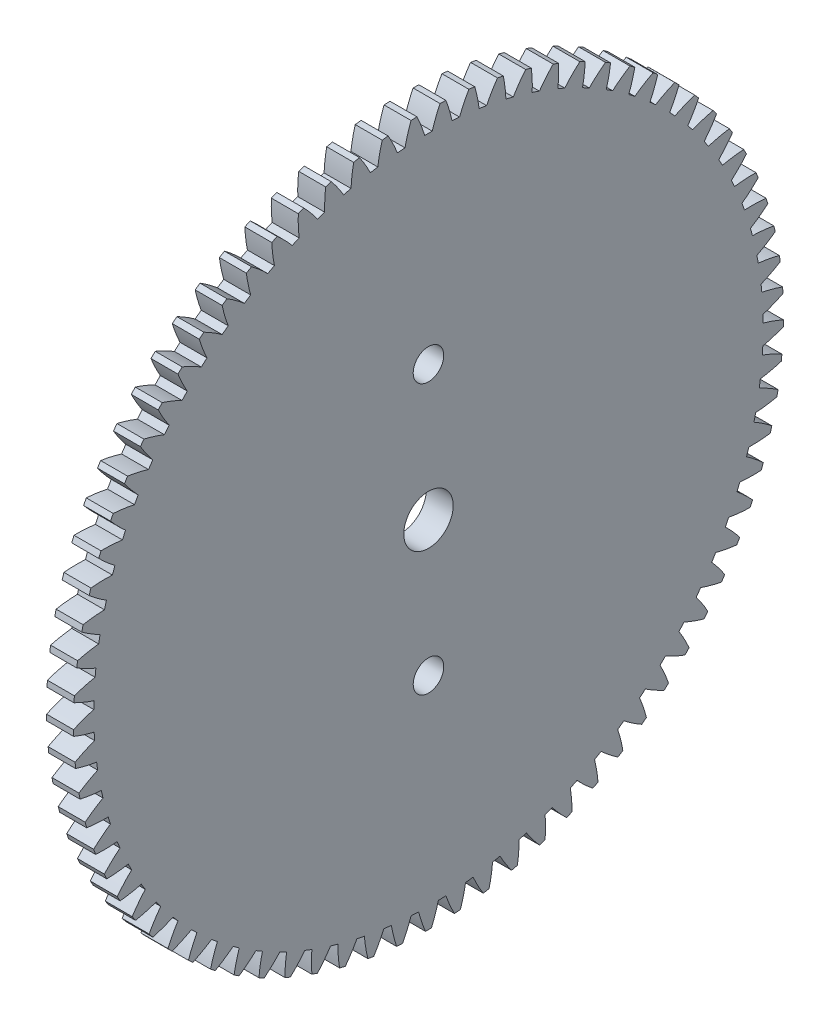
SolidWorks part; units mm, degrees
ref_plane "Plane1" through (0, 0, 0) normal (0, 0, 1) x (1, 0, 0)
ref_plane "Plane2" through (0, 0, 0) normal (0, 1, 0) x (1, 0, 0)
ref_plane "Plane3" through (0, 0, 0) normal (1, 0, 0) x (0, 0, -1)
sketch "HoldingSke" plane through (0, 0, 0) normal (0, 1, 0) x (1, 0, 0)
  line L0 (0, 0) -> (0.225, -0.9744)
  line L1 (-15, 0) -> (100, 0) construction
  line L2 (0, 0) -> (-2.1039, 2.3779)
  line L3 (0, 0) -> (-11.863, 4.5341)
  line L4 (0, 0) -> (1.9427, 8.4147)
  line L5 (0, 0) -> (-46.8476, -17.4728)
  line L6 (0, 0) -> (-1.6579, -1.1186)
  line L7 (-2.1039, 2.3779) -> (8.6586, 51.2059)
  line L8 (-76.2, 54.61) -> (-76.1, 54.61)
  line L9 (-71.009, 38.7566) -> (-53.1078, 45.2721)
  line L10 (-76.2, 71.12) -> (104.1128, 71.12)
  line L11 (0, 0) -> (-2, 0)
  line L12 (-76.2, 101.6) -> (-76.162, 101.6)
  line L13 (24.9733, 27.94) -> (52.9518, 28.4284)
  line L14 (24.9733, 27.94) -> (24.9743, 27.94)
  line L15 (24.9733, 27.94) -> (100.4006, 29.5858)
  line L16 (-63.627, -1) -> (-12.827, -1)
  circle A0 centre (0, 0) radius 0.5
  circle A1 centre (0, 0) radius 37.249
  circle A2 centre (0, 0) radius 37.5
  circle A3 centre (0, 0) radius 0.5
  dimension "MHD" = 74.498
  dimension "Hub_dia" = 75
  dimension "Bore" = 1
  dimension "MBD" = 1
  dimension "Num_teeth" = 77
  dimension "Pitch" = 1
  dimension "Overall_len" = 50
  dimension "Show_teeth" = 77
  dimension "Thickness" = 2
  dimension "OAL" = 50.0001
  dimension "T_dim" = 0.1
  dimension "Ap" = 20
  dimension "H" = 19.05
  dimension "Pitch_radius" = 180.3128
  dimension "Width" = 2
  dimension "Backlash" = 0.038
  dimension "Addendum_fac" = 1
  dimension "Dedendum_fac" = 1.25
  dimension "Clearance_fac" = 0.25
  dimension "Dedendum_add" = 0.001
  dimension "Module" = 1
sketch "BasProSke" plane through (0, 0, 0) normal (0, 1, 0) x (1, 0, 0)
  line L0 (-10, 0) -> (60, 0) construction
  line L1 (0, 0) -> (0, 39.5)
  line L2 (0, 0) -> (2, 0)
  line L3 (2, 0) -> (2, 39.5)
  line L4 (2, 39.5) -> (0, 39.5)
  dimension "Thickness" = 2
  dimension "Diameter" = 79
revolve "Base-Revolve" add sketch "BasProSke" angle 360 about L0
sketch "TooCutSke" plane through (0, 0, 0) normal (1, 0, 0) x (0, 0, -1)
  line L1 (0, 0) -> (0, 107) construction
  line L2 (0, 0) -> (-0.8518, 38.4906) construction
  line L3 (0, 0) -> (-3.1402, 76.9225) construction
  line L4 (-0.8518, 38.4906) -> (-1.5701, 38.4613) construction
  arc A0 (0.4217, 37.2466) -> (-0.4217, 37.2466) centre (0, 0) ccw
  arc A1 (1.2943, 39.5042) -> (-1.2943, 39.5042) centre (0, 0) ccw
  circle A2 centre (0, 0) radius 38.5 construction
  circle A3 centre (0, 0) radius 36.1782 construction
  arc A4 (-0.4217, 37.2466) -> (-1.2943, 39.5042) centre (-15.1779, 32.8404) ccw
  arc A5 (1.2943, 39.5042) -> (0.4217, 37.2466) centre (15.1779, 32.8404) ccw
  dimension "Root_dia" = 74.498
  dimension "Overcut_dia" = 79.0508
  dimension "Pitch_dia" = 77
  dimension "Base_dia" = 72.3563
  dimension "Flank_rad" = 15.4
  dimension "Half_ang" = 2.338
  dimension "Half_CT" = 0.7188
extrude "ToothCut" cut sketch "TooCutSke" along normal through all
fillet "Breaks" [suppressed] radius 0.02 tangent propagation no
fillet "RootFillets" [suppressed] radius 0.251
pattern_circular "TeethCuts" count 77 every 4.675 about axis through (-10, 0, 0) along (1, 0, 0) of "ToothCut", "RootFillets", "Breaks"
sketch "HubNeaOneSke" plane through (0, 0, 0) normal (-1, 0, 0) x (0, 0, 1)
  circle A0 centre (0, 0) radius 37.249
  dimension "Diameter" = 74.498
extrude "HubNearOne" [suppressed] add sketch "HubNeaOneSke" along normal blind 48.0001
sketch "HubNeaBotSke" plane through (0, 0, 0) normal (-1, 0, 0) x (0, 0, 1)
  circle A0 centre (0, 0) radius 37.249
  dimension "Diameter" = 74.498
extrude "HubNearBoth" [suppressed] add sketch "HubNeaBotSke" along normal blind 24
ref_plane "FarPln" through (2, 0, 0) normal (1, 0, 0) x (0, 0, -1)
sketch "HubFarSke" plane through (2, 0, 0) normal (1, 0, 0) x (0, 0, -1)
  circle A0 centre (0, 0) radius 37.249
  dimension "Diameter" = 74.498
extrude "HubFar" [suppressed] add sketch "HubFarSke" along normal blind 24
sketch "BorSke" plane through (0, 0, 0) normal (1, 0, 0) x (0, 0, -1)
  circle A0 centre (0, 0) radius 2.75
  circle A1 centre (0, -15) radius 1.7
  circle A2 centre (0, 15) radius 1.7
  dimension "Diameter" = 5.5
  dimension "D3" = 3.4
  dimension "D4" = 3.4
  dimension "D1" = 15
  dimension "D2" = 15
extrude "Bore" cut sketch "BorSke" along normal mid plane 100.0001
sketch "KeySke" plane through (0, 0, 0) normal (1, 0, 0) x (0, 0, -1)
  line L0 (-0.05, 0) -> (-0.05, 0.6)
  line L1 (-0.05, 0.6) -> (0.05, 0.6)
  line L2 (0.05, 0.6) -> (0.05, 0)
  line L3 (0, 0) -> (0, 34) construction
  line L4 (-0.05, 0) -> (0.05, 0)
  dimension "Offset" = 0.6
  dimension "Width" = 0.1
extrude "Keyway" [suppressed] cut sketch "KeySke" along normal mid plane 100.0001
pattern_circular "Keyway2" [suppressed] count 2 every 90 about axis through (-10, 0, 0) along (1, 0, 0) reverse direction yes
scale "Scale1" scale about centroid uniform scaling no x scale factor 1.5 y scale factor 1 z scale factor 1
equation "' \"Module@HoldingSke\" = 6.35"
equation "' \"Num_teeth@HoldingSke\" = 12"
equation "' \"Ap@HoldingSke\" =  20"
equation "' \"Ap@HoldingSke\" = 20"
equation "' \"Width@HoldingSke\" = 0.5 * 25.4"
equation "' \"Hub_dia@HoldingSke\"= 1 * 25.4"
equation "' \"Hub_dia@HoldingSke\" = 1 * 25.4"
equation "' \"Overall_len@HoldingSke\" = 1.0 * 25.4"
equation "' \"Bore@HoldingSke\" = 0.75 * 25.4"
equation "' \"T_dim@HoldingSke\" = 0.1 * 25.4"
equation "' \"Width@KeySke\" = 0.25 * 25.4"
equation "' \"Show_teeth@HoldingSke\" = 13"
equation "' \"Backlash@HoldingSke\" = 0.009 * 25.4"
equation "' \"Addendum_fac@HoldingSke\" = 1.0"
equation "' \"Dedendum_fac@HoldingSke\" = 1.25"
equation "' \"Dedendum_add@HoldingSke\" = 0.00005 * 25.4"
equation "' \"Clearance_fac@HoldingSke\" = 0.25"
equation "\"Pitch@HoldingSke\" = 1 / \"Module@HoldingSke\""
equation "\"Overcut_dia@TooCutSke\" = (\"Num_teeth@HoldingSke\" + 2 * \"Addendum_fac@HoldingSke\") / \"Pitch@HoldingSke\" + 0.002 * 25.4"
equation "\"Pitch_dia@TooCutSke\" = \"Num_teeth@HoldingSke\" / \"Pitch@HoldingSke\""
equation "\"Base_dia@TooCutSke\" = \"Num_teeth@HoldingSke\" / \"Pitch@HoldingSke\" * cos((\"Ap@HoldingSke\"  * 3.14159265 / 180))"
equation "\"Root_dia@TooCutSke\" = (\"Num_teeth@HoldingSke\" + 2) / \"Pitch@HoldingSke\" - 2 * (\"Addendum_fac@HoldingSke\" + \"Dedendum_fac@HoldingSke\") / \"Pitch@HoldingSke\" - \"Dedendum_add@HoldingSke\" * 2"
equation "\"Half_ang@TooCutSke\" = 180 / \"Num_teeth@HoldingSke\""
equation "\"Half_CT@TooCutSke\" = \"Num_teeth@HoldingSke\" / \"Pitch@HoldingSke\" * sin((3.14159265 / 2 / \"Num_teeth@HoldingSke\")) / 2 - 7 * \"Backlash@HoldingSke\" / 4"
equation "\"Flank_rad@TooCutSke\" = \"Num_teeth@HoldingSke\" / \"Pitch@HoldingSke\" / 5"
equation "\"Radius@RootFillets\" = \"Clearance_fac@HoldingSke\" / \"Pitch@HoldingSke\" + \"Dedendum_add@HoldingSke\""
equation "\"Break_rad@Breaks\" = 0.02 / \"Pitch@HoldingSke\""
equation "\"Thickness@HoldingSke\" = \"Width@HoldingSke\""
equation "\"OAL@HoldingSke\" = \"Thickness@HoldingSke\""
equation "\"MHD@HoldingSke\" = (\"Num_teeth@HoldingSke\" + 2) / \"Pitch@HoldingSke\" - 2 * (\"Addendum_fac@HoldingSke\" + \"Dedendum_fac@HoldingSke\")  / \"Pitch@HoldingSke\" - \"Dedendum_add@HoldingSke\" * 2"
equation "\"MBD@HoldingSke\" = (\"Num_teeth@HoldingSke\" + 2) / \"Pitch@HoldingSke\" - 2 * (\"Addendum_fac@HoldingSke\" + \"Dedendum_fac@HoldingSke\")  / \"Pitch@HoldingSke\" - \"Dedendum_add@HoldingSke\" * 2 - 0.002 * 25.4"
equation "\"MHD@HoldingSke\" = ((sgn( \"MHD@HoldingSke\" - \"Hub_dia@HoldingSke\" )-1)*( \"MHD@HoldingSke\" - \"Hub_dia@HoldingSke\" ))/-2+ \"Hub_dia@HoldingSke\""
equation "\"MBD@HoldingSke\" = ((sgn( \"MBD@HoldingSke\" - \"Bore@HoldingSke\" )-1)*( \"MBD@HoldingSke\" - \"Bore@HoldingSke\" ))/-2+ \"Bore@HoldingSke\""
equation "\"OAL@HoldingSke\" = ((sgn( \"OAL@HoldingSke\" - \"Overall_len@HoldingSke\" )+1)*( \"OAL@HoldingSke\" - \"Overall_len@HoldingSke\" ))/2 + \"Overall_len@HoldingSke\" + 0.000002 * 25.4"
equation "\"Num_teeth@TeethCuts\" = int( \"Show_teeth@HoldingSke\" ) + 1"
equation "\"Num_teeth@TeethCuts\" = ((sgn( \"Num_teeth@TeethCuts\" - \"Num_teeth@HoldingSke\" )-1)*( \"Num_teeth@TeethCuts\" - \"Num_teeth@HoldingSke\" ))/-2+ \"Num_teeth@HoldingSke\""
equation "\"Num_teeth@TeethCuts\" = ((sgn( \"Num_teeth@TeethCuts\" - 2.0)+1)*( \"Num_teeth@TeethCuts\" - 2.0))/2 +2.0"
equation "\"Angle@TeethCuts\" = 360.0 / \"Num_teeth@HoldingSke\""
equation "\"Diameter@BasProSke\" = (\"Num_teeth@HoldingSke\" + 2 * \"Addendum_fac@HoldingSke\") / \"Pitch@HoldingSke\""
equation "\"Thickness@BasProSke\"  = \"Thickness@HoldingSke\""
equation "' \"Fillet_rad@BasProSke\" =  \"Thickness@HoldingSke\" * 0.05"
equation "' \"Fillet_rad@BasProSke\" = \"Thickness@HoldingSke\" * 0.05"
equation "\"MHD@HoldingSke\" = ((sgn( \"MHD@HoldingSke\" - \"Root_dia@TooCutSke\" )-1)*( \"MHD@HoldingSke\" - \"Root_dia@TooCutSke\" ))/-2+ \"Root_dia@TooCutSke\""
equation "\"Diameter@HubNeaOneSke\" = \"MHD@HoldingSke\""
equation "\"Length@HubNearOne\" = \"OAL@HoldingSke\" - \"Thickness@BasProSke\""
equation "\"Diameter@HubNeaBotSke\" = \"MHD@HoldingSke\""
equation "\"Length@HubNearBoth\" = ( \"OAL@HoldingSke\" - \"Thickness@BasProSke\" ) / 2.0"
equation "\"Thickness@FarPln\" = \"Thickness@BasProSke\""
equation "\"Diameter@HubFarSke\" = \"MHD@HoldingSke\""
equation "\"Length@HubFar\" = ( \"OAL@HoldingSke\" - \"Thickness@BasProSke\" ) / 2.0"
equation "\"Diameter@BorSke\"=5.5mm"
equation "\"D1@Bore\" = \"OAL@HoldingSke\" * 2.0"
equation "\"D1@Keyway\" = \"OAL@HoldingSke\" * 2.0"
equation "\"Offset@KeySke\" = \"T_dim@HoldingSke\" + \"MBD@HoldingSke\" / 2.0"
